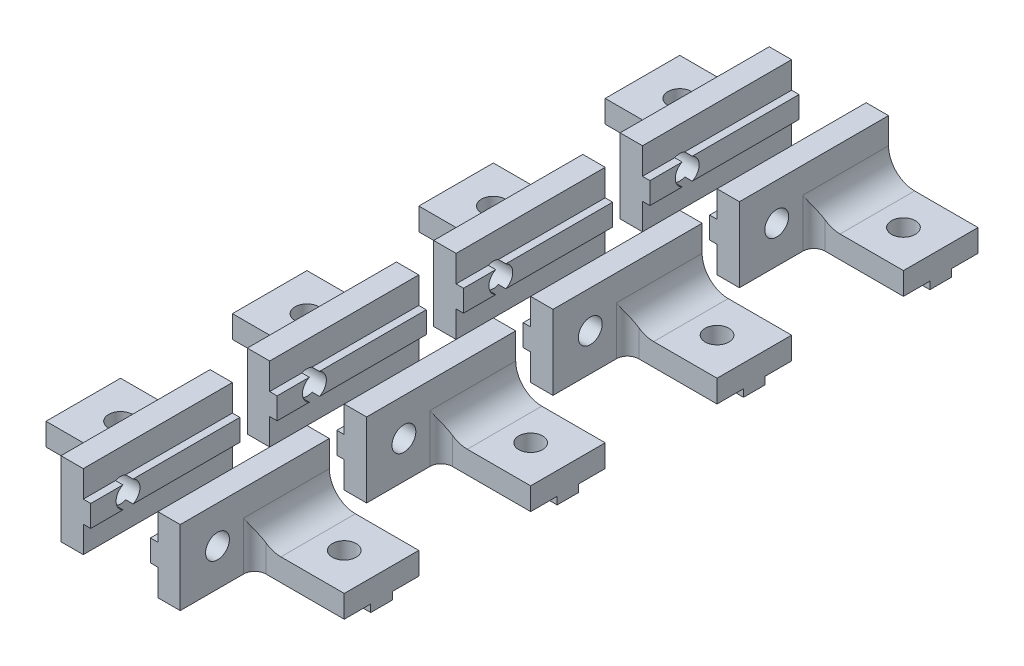
SolidWorks part; units mm, degrees
ref_plane "Front Plane" through (0, 0, 0) normal (0, 0, 1) x (1, 0, 0)
ref_plane "Top Plane" through (0, 0, 0) normal (0, 1, 0) x (1, 0, 0)
ref_plane "Right Plane" through (0, 0, 0) normal (1, 0, 0) x (0, 0, -1)
sketch "Esquisse1" plane through (0, 0, 0) normal (0, 0, 1) x (1, 0, 0)
  line L0 (0, 0) -> (15, 0)
  line L1 (15, 0) -> (15, 3)
  line L2 (15, 3) -> (6.5, 3)
  line L4 (3, 6.5) -> (3, 10)
  line L5 (3, 10) -> (0, 10)
  line L6 (0, 10) -> (0, 0)
  arc A0 (6.5, 3) -> (3, 6.5) centre (6.5, 6.5) cw
  dimension "D1" = 3.5
  dimension "D2" = 10
  dimension "D3" = 3
  dimension "D4" = 15
extrude "Main" add sketch "Esquisse1" along normal blind 20
sketch "Esquisse4" plane through (0, 0, 0) normal (-1, 0, 0) x (0, 0, 1)
  line L0 (20, 10) -> (0, 10) construction
  line L1 (0, 6.45) -> (20, 6.45)
  line L2 (0, 6.45) -> (0, 3.55)
  line L3 (0, 3.55) -> (20, 3.55)
  line L4 (20, 6.45) -> (20, 3.55)
  line L6 (0, 10) -> (0, 0) construction
  line L7 (20, 10) -> (20, 0) construction
  dimension "D1" = 2.9
  dimension "D2" = 3.55
extrude "VerticalGuidance" add sketch "Esquisse4" along normal blind 1
sketch "Esquisse2" plane through (0, 0, 0) normal (-1, 0, 0) x (0, 0, 1)
  line L4 (20, 6.5) -> (20, 10) construction
  line L5 (20, 0) -> (0, 0) construction
  circle A0 centre (15, 5) radius 1.6
  dimension "D1" = 3.2
  dimension "D2" = 5
  dimension "D3" = 5
extrude "VerticalHole" cut sketch "Esquisse2" against normal through all both and the other way through all
sketch "Esquisse5" plane through (0, 0, 0) normal (0, -1, 0) x (-1, 0, 0)
  line L1 (0, -3.55) -> (-15, -3.55)
  line L2 (0, -3.55) -> (0, -6.45)
  line L3 (0, -6.45) -> (-15, -6.45)
  line L4 (-15, -3.55) -> (-15, -6.45)
  line L8 (0, 0) -> (0, -14.3236) construction
  line L9 (-15, -20) -> (-15, 0) construction
  line L10 (0, 0) -> (-15, 0) construction
  dimension "D1" = 2.9
  dimension "D2" = 3.55
extrude "HorizontalGuidance" add sketch "Esquisse5" along normal blind 1
sketch "Esquisse3" plane through (0, 3, 0) normal (0, -1, 0) x (1, 0, 0)
  line L5 (15, 20) -> (15, 0) construction
  line L8 (15, 0) -> (6.5, 0) construction
  circle A0 centre (10, 5) radius 1.6
  dimension "D1" = 5
  dimension "D2" = 5
  dimension "D3" = 3.2
extrude "HorizontalHole" cut sketch "Esquisse3" against normal through all both and the other way through all
sketch "Esquisse9" plane through (0, 3, 0) normal (0, 1, 0) x (1, 0, 0)
  line L0 (15, -20) -> (15, 0) construction
  line L1 (3, -20) -> (15, -20)
  line L2 (3, -20) -> (3, -10)
  line L3 (3, -10) -> (15, -10)
  line L4 (15, -20) -> (15, -10)
  line L5 (15, 0) -> (6.5, 0) construction
  dimension "D1" = 10
extrude "Enlèv. mat.-Extru.4" cut sketch "Esquisse9" against normal through all both and the other way through all
fillet "Congé2" radius 1.5 1 edges at (3, 3.25, 10)
ref_plane "SymetryPlan" through (-5, 0, 0) normal (1, 0, 0) x (0, 0, -1)
ref_axis "Axe1" through (-5, 0, -4.75) along (0, 0, 1)
pattern_linear "Répétition linéaire1" count 4 spacing 25 along (0, 0, 1) of bodies 113 114
mirror "Symétrie3" about plane through (-5, 0, 0) normal (1, 0, 0) of bodies 115 113 116 117
